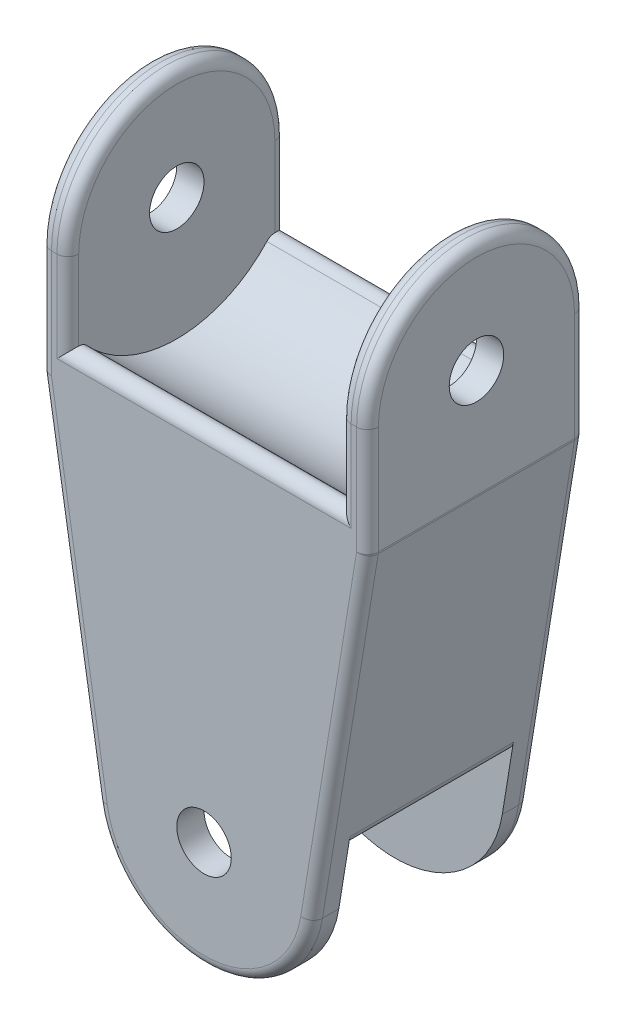
SolidWorks part; units mm, degrees
material "ABS"
ref_plane "Front Plane" through (0, 0, 0) normal (0, 0, 1) x (1, 0, 0)
ref_plane "Top Plane" through (0, 0, 0) normal (0, 1, 0) x (1, 0, 0)
ref_plane "Right Plane" through (0, 0, 0) normal (1, 0, 0) x (0, 0, -1)
sketch "Sketch1" plane through (0, 0, 0) normal (0, 0, 1) x (1, 0, 0)
  line L0 (-38.1, 76.2) -> (-25.0719, -4.0693)
  line L1 (38.1, 76.2) -> (38.1, 127)
  line L2 (25.0719, -4.0693) -> (38.1, 76.2)
  line L3 (38.1, 127) -> (-38.1, 127)
  line L4 (-38.1, 127) -> (-38.1, 76.2)
  arc A0 (-25.0719, -4.0693) -> (25.0719, -4.0693) centre (0, 0) ccw
  circle A2 centre (0, 0) radius 6.35
  dimension "D2" = 25.4
  dimension "D4" = 12.7
  dimension "D1" = 76.2
  dimension "D3" = 76.2
  dimension "D5" = 50.8
extrude "Boss-Extrude1" add sketch "Sketch1" along normal blind 6.35 contours L0 A0 L2 L1 L3 L4 A2 region at (0, 60.2384, 0)
sketch "Sketch2" plane through (0, 0, 0) normal (0, 0, -1) x (-1, 0, 0)
  line L0 (-25.0719, -4.0693) -> (-38.1, 76.2)
  line L1 (-38.1, 76.2) -> (-38.1, 127)
  line L2 (-38.1, 127) -> (38.1, 127)
  line L3 (38.1, 127) -> (38.1, 76.2)
  line L4 (38.1, 76.2) -> (25.0719, -4.0693)
  line L5 (-25.0719, -4.0693) -> (-38.1, 76.2) construction
  circle A0 centre (0, 0) radius 25.4
  arc A2 (-25.0719, -4.0693) -> (25.0719, -4.0693) centre (0, 0) ccw construction
  line M4 (38.1, 76.2) -> (38.1, 127)
  line M5 (38.1, 127) -> (-38.1, 127)
  line M6 (-38.1, 127) -> (-38.1, 76.2)
extrude "Boss-Extrude2" add sketch "Sketch2" along normal blind 38.1 contours A0 L4 L0 M4 M5 M6 region at (0, 75.0604, 0)
sketch "Sketch3" plane through (0, 0, -38.1) normal (0, 0, -1) x (-1, 0, 0)
  line L0 (-38.1, 76.2) -> (-25.0719, -4.0693)
  line L1 (38.1, 76.2) -> (38.1, 127)
  line L2 (25.0719, -4.0693) -> (38.1, 76.2)
  line L3 (38.1, 127) -> (-38.1, 127)
  line L4 (-38.1, 127) -> (-38.1, 76.2)
  line L5 (-38.1, 76.2) -> (-25.0719, -4.0693) construction
  arc A0 (-25.0719, -4.0693) -> (25.0719, -4.0693) centre (0, 0) ccw
  circle A1 centre (0, 0) radius 6.35
  dimension "D2" = 25.4
  dimension "D4" = 12.7
extrude "Boss-Extrude3" add sketch "Sketch3" along normal blind 6.35
sketch "Sketch4" plane through (-38.1, 0, 0) normal (-1, 0, 0) x (0, 0, 1)
  line L0 (-44.45, 76.2) -> (-44.45, 127) construction
  line L1 (6.35, 127) -> (6.35, 76.2) construction
  line L3 (0, 0) -> (6.35, 0)
  line L4 (6.35, 76.2) -> (6.35, -4.0693) construction
  line L5 (6.35, 127) -> (-44.45, 127) construction
  circle A0 centre (-19.05, 101.6) radius 6.35
  arc A1 (-44.45, 101.6) -> (6.35, 101.6) centre (-19.05, 101.6) cw
  point P17 (-19.05, 127)
  line M4 (-44.45, 127) -> (-44.45, 76.2)
  line M6 (6.35, 76.2) -> (6.35, 127)
  line M8 (6.35, 127) -> (-44.45, 127)
  dimension ".5" = 12.7
  dimension "D1" = 101.6
extrude "Cut-Extrude1" cut sketch "Sketch4" against normal through all contours A1 M4 M8 | A1 M8 M6 | A0 region at (-38.1, 101.6, -19.05) region at (-38.1, 121.3265, -38.7765) region at (-38.1, 121.3265, 0.6765)
ref_plane "Plane2" through (-31.75, 0, 0) normal (-1, 0, 0) x (0, 0, 1)
sketch "Sketch6" plane through (-31.75, 0, 0) normal (-1, 0, 0) x (0, 0, 1)
  circle A0 centre (-19.05, 101.6) radius 28.575
  dimension "D1" = 57.15
extrude "Cut-Extrude3" cut sketch "Sketch6" against normal blind 63.5
fillet "Fillet3" radius 2.54 25 edges at (-31.75, 127, -19.05) (-38.1, 127, -19.05) (38.1, 127, -19.05) (31.75, 127, -19.05) (38.1, 76.2, -19.05) (25.0719, -4.0693, -19.05) (38.1, 88.9, 6.35) (31.586, 36.0654, 6.35) (0, -25.4, 6.35) (-38.1, 88.9, 6.35) (-31.75, 95.0546, 6.35) (0, 88.5091, 6.35) (31.75, 95.0546, 6.35) (-31.586, 36.0654, 6.35) (-25.0719, -4.0693, -19.05) (-38.1, 76.2, -19.05) (-31.75, 95.0546, -44.45) (-38.1, 88.9, -44.45) (-31.586, 36.0654, -44.45) (0, -25.4, -44.45) (31.586, 36.0654, -44.45) (38.1, 88.9, -44.45) (31.75, 95.0546, -44.45) (0, 88.5091, -44.45) (-6.35, 0, -44.45)
